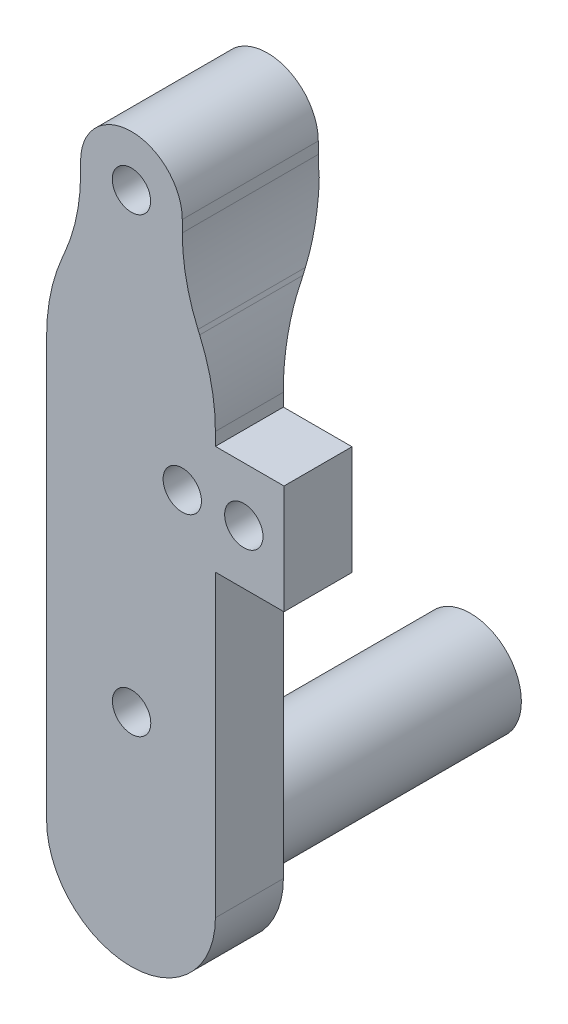
SolidWorks part; units mm, degrees
ref_plane "Front Plane" through (0, 0, 0) normal (0, 0, 1) x (1, 0, 0)
ref_plane "Top Plane" through (0, 0, 0) normal (0, 1, 0) x (1, 0, 0)
ref_plane "Right Plane" through (0, 0, 0) normal (1, 0, 0) x (0, 0, -1)
sketch "Sketch1" plane through (0, 0, 0) normal (0, 0, 1) x (1, 0, 0)
  line L0 (-5.898, 28.3342) -> (-5.898, 27.2476)
  line L1 (-2.8056, 11.5313) -> (-2.8056, 12.738)
  line L2 (3.6016, 11.5313) -> (3.6016, 1.3594)
  line L3 (-18.5662, 11.5313) -> (-18.5662, -26.5933)
  line L4 (3.6016, 1.3594) -> (-2.8056, 1.3594)
  line L5 (-2.8056, -26.5933) -> (-2.8056, 1.3594)
  line L6 (3.6016, 11.5313) -> (-2.8056, 11.5313)
  line L7 (-16.8793, 20.1661) -> (-17.0781, 19.7113)
  line L8 (-2.8056, 11.5313) -> (-18.5662, 11.5313) construction
  line L9 (-18.5662, 11.5313) -> (-18.5662, 12.5907)
  line L10 (-15.3912, 28.3342) -> (-15.3912, 27.2867)
  line L11 (-10.6859, -34.4736) -> (-36.5829, -34.4736) construction
  line L12 (-4.2728, 19.8107) -> (-4.4307, 20.1749)
  circle A0 centre (-10.6446, 28.3342) radius 1.7907
  circle A1 centre (-0.1512, 6.4513) radius 1.7907
  circle A2 centre (-5.898, 6.4513) radius 1.7907
  circle A3 centre (-10.6446, 28.3342) radius 4.7466
  circle A4 centre (-10.6859, -26.5933) radius 7.8803
  arc A5 (-18.5662, 12.5907) -> (-17.0781, 19.7113) centre (-0.7862, 12.5907) cw
  arc A6 (-15.3912, 27.2867) -> (-16.8793, 20.1661) centre (-33.1712, 27.2867) cw
  arc A7 (-5.898, 27.2476) -> (-4.4307, 20.1749) centre (11.882, 27.2476) ccw
  arc A8 (-2.8056, 12.738) -> (-4.2728, 19.8107) centre (-20.5856, 12.738) ccw
  circle A9 centre (-10.6287, -13.8687) radius 1.7907
  dimension "D1" = 17.78
  dimension "D2" = 3.5814
  dimension "D3" = 15.7606
  dimension "D4" = 3.5814
  dimension "D5" = 3.5814
  dimension "D6" = 7.9375
  dimension "D7" = 20.32
  dimension "D8" = 5.08
extrude "Boss-Extrude1" add sketch "Sketch1" along normal blind 12.7 contours A4 | L6 L8 L3 A4 L5 L4 L2 A2 A1 A9 | L8 L1 A8 L12 A7 L0 A3 L10 A6 L7 A5 L9 | A3 A0 region at (-10.6446, 23.7219, 0) region at (-9.8877, 1.7898, 0) region at (-10.6859, -26.5933, 0)
ref_plane "Plane2" through (0, -34.4736, 0) normal (0, -1, 0) x (-1, 0, 0)
sketch "Sketch8" plane through (-18.5662, 0, -18.5662) normal (1, 0, 0) x (0, 0, -1)
  line L0 (-24.9162, -34.4736) -> (-18.5662, -34.4736)
  line L1 (-18.5662, -34.4736) -> (-18.5662, 27.6449)
  line L2 (-37.6162, -34.4736) -> (-43.9662, -34.4736)
  line L3 (-43.9662, -34.4736) -> (-43.9662, 27.6449)
  line L4 (-37.6162, 11.2679) -> (-37.6162, 12.9164)
  line L6 (-37.6162, -34.4736) -> (-37.6162, 11.2679)
  line L7 (-24.9162, -34.4736) -> (-24.9162, 11.2679)
  line L8 (-24.9162, 11.2679) -> (-24.9162, 12.9164)
  line L9 (-40.3517, 19.2772) -> (-41.3009, 20.1766)
  line L10 (-22.1806, 19.2772) -> (-21.2315, 20.1766)
  line L13 (-18.5662, -26.5933) -> (-18.5662, 12.5907) construction
  line L14 (-25.5512, -34.4736) -> (-11.5812, -34.4736) construction
  arc A0 (-24.9162, 12.9164) -> (-22.1806, 19.2772) centre (-16.1532, 12.9164) cw
  arc A1 (-37.6162, 12.9164) -> (-40.3517, 19.2772) centre (-46.3792, 12.9164) ccw
  arc A2 (-18.5662, 27.6449) -> (-21.2315, 20.1766) centre (-27.2589, 26.5374) cw
  arc A3 (-43.9662, 27.6449) -> (-41.3009, 20.1766) centre (-35.2735, 26.5374) ccw
  line M27 (-18.5662, -26.5933) -> (-31.2662, -26.5933)
  line M29 (-31.2662, 12.5907) -> (-18.5662, 12.5907)
  line M30 (-18.5662, 12.5907) -> (-18.5662, -26.5933)
  dimension "D1" = 8.763
  dimension "D2" = 1.3076
  dimension "D3" = 6.35
  dimension "D4" = 12.7
  dimension "D5" = 62.1185
  dimension "D6" = 45.7414
  dimension "D7" = 1.6485
extrude "Cut-Extrude7" cut sketch "Sketch8" along normal up to surface (22.1678 mm away) contours L7 L8 M29 M30 M27 | A2 L1 L8 A0 L10 M29 | L0 L7 L1 M27 region at (-18.5662, -30.5334, 3.175) region at (-18.5662, -7.0013, 3.175) region at (-18.5662, 16.5852, 2.5234) up to face at (3.6016, 6.4454, 6.35)
sketch "Sketch9" plane through (0, 0, 6.35) normal (0, 0, -1) x (-1, 0, 0)
  circle A0 centre (10.7431, -26.5687) radius 4.7625
  circle A1 centre (10.7431, -26.5687) radius 5.715 construction
  dimension "D1" = 9.525
extrude "Boss-Extrude2" add sketch "Sketch9" along normal blind 25.4
